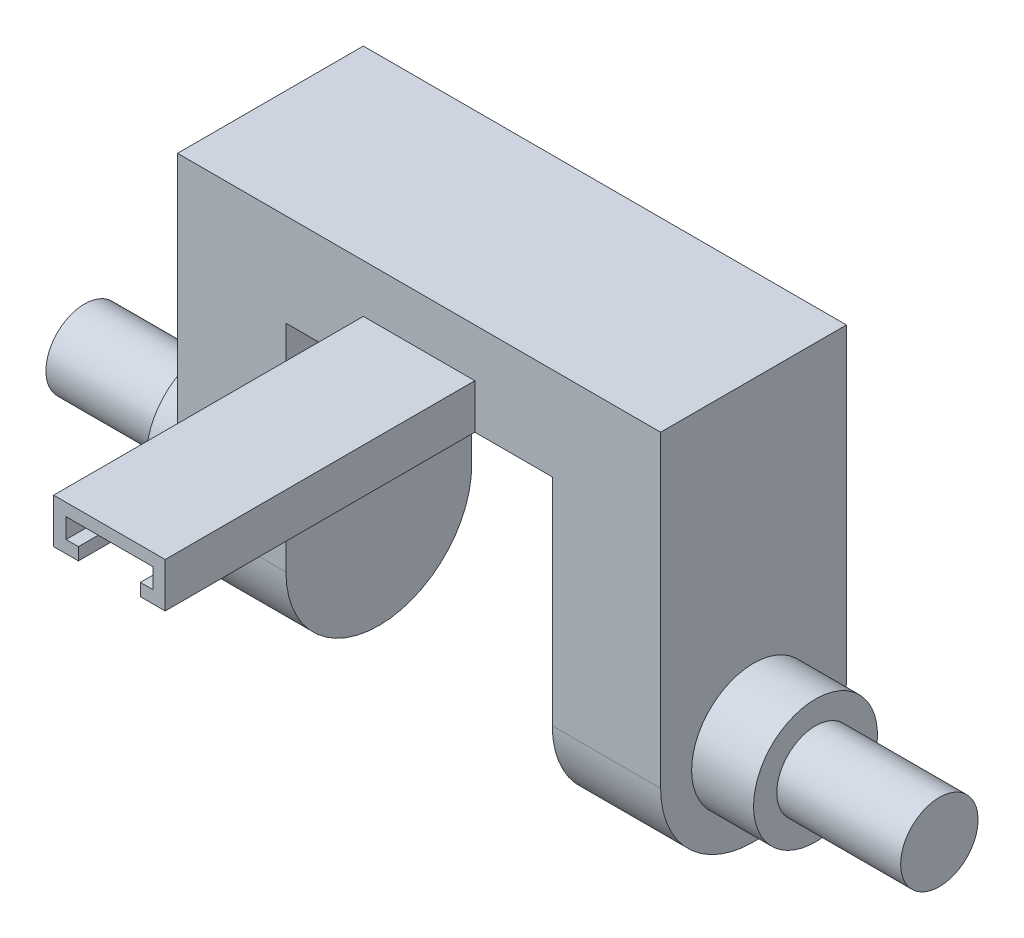
SolidWorks part; units mm, degrees
other "Markup1"
sketch "Sketch11" plane through (-87.63, 12.446, 0) normal (-0.7828, 0.0559, -0.6197) x (-0.6207, 0, 0.7841)
ref_plane "Front Plane" through (0, 0, 0) normal (0, 0, 1) x (1, 0, 0)
ref_plane "Top Plane" through (0, 0, 0) normal (0, 1, 0) x (1, 0, 0)
ref_plane "Right Plane" through (0, 0, 0) normal (1, 0, 0) x (0, 0, -1)
sketch "Sketch1" plane through (0, 0, 0) normal (0, 0, 1) x (1, 0, 0)
  line L0 (8.89, 0) -> (-8.89, 0)
  line L1 (-8.89, 0) -> (-8.89, -4.064)
  line L2 (-8.89, -4.064) -> (-6.35, -4.064)
  line L3 (-6.35, -4.064) -> (-6.35, -6.604)
  line L4 (-6.35, -6.604) -> (-11.43, -6.604)
  line L5 (-11.43, -6.604) -> (-11.43, 2.54)
  line L6 (-11.43, 2.54) -> (11.43, 2.54)
  line L7 (0, 2.54) -> (0, 0) construction
  line L8 (11.43, -6.604) -> (11.43, 2.54)
  line L9 (6.35, -6.604) -> (11.43, -6.604)
  line L10 (6.35, -4.064) -> (6.35, -6.604)
  line L11 (8.89, -4.064) -> (6.35, -4.064)
  line L12 (8.89, 0) -> (8.89, -4.064)
  dimension "D1" = 17.78
  dimension "D2" = 12.7
  dimension "D3" = 4.064
  dimension "D4" = 2.54
  dimension "D5" = 2.54
  dimension "D6" = 2.54
extrude "Rail Grip" add sketch "Sketch1" along normal blind 101.6
sketch "Sketch2" plane through (0, 0, 0) normal (0, -1, 0) x (1, 0, 0)
  line L1 (-3.175, 31.75) -> (3.175, 31.75)
  line L2 (-3.175, 31.75) -> (-3.175, 0)
  line L3 (-3.175, 0) -> (3.175, 0)
  line L4 (3.175, 31.75) -> (3.175, 0)
  line L5 (-3.175, 31.75) -> (3.175, 0) construction
  line L6 (-3.175, 0) -> (3.175, 31.75) construction
  point P0 (0, 15.875)
  dimension "D1" = 6.35
  dimension "D2" = 31.75
  dimension "D3" = 31.75
extrude "Rail Notch" add sketch "Sketch2" along normal blind 1.27
chamfer "Chamfer1" distance 0.254 angle 45 3 edges at (-3.175, -1.27, 15.875) (3.175, -1.27, 15.875) (0, -1.27, 31.75)
sketch "Sketch5" plane through (0, 0, 0) normal (0, 0, -1) x (-1, 0, 0)
  line L0 (8.89, -4.064) -> (8.89, -6.604)
  line L1 (11.43, -6.604) -> (6.35, -6.604) construction
  line L2 (8.89, -6.604) -> (6.35, -6.604)
  line L3 (6.35, -6.604) -> (6.35, -4.064)
  line L4 (6.35, -4.064) -> (8.89, -4.064)
  line L5 (-6.35, -4.064) -> (-8.89, -4.064)
  line L6 (-8.89, -4.064) -> (-8.89, -6.604)
  line L7 (-6.35, -6.604) -> (-11.43, -6.604) construction
  line L8 (-8.89, -6.604) -> (-6.35, -6.604)
  line L9 (-6.35, -6.604) -> (-6.35, -4.064)
extrude "Cut-Extrude1" cut sketch "Sketch5" against normal blind 53.975
sketch "Sketch4" plane through (0, 0, 0) normal (1, 0, 0) x (0, 0, -1)
  line L0 (0, 2.54) -> (0, 21.59)
  line L2 (-101.6, 2.54) -> (0, 2.54) construction
  line L3 (-65.0408, 2.54) -> (0, 2.54)
  line L4 (-32.5204, 35.0604) -> (-65.0408, 2.54)
  line L5 (0, -6.604) -> (0, 2.54) construction
  circle A1 centre (-19.05, 21.59) radius 7.9375
  arc A2 (0, 21.59) -> (-32.5204, 35.0604) centre (-19.05, 21.59) ccw
  dimension "D2" = 19.05
  dimension "D3" = 15.875
  dimension "D1" = 45
  dimension "D4" = 19.05
  dimension "D5" = 19.05
extrude "Boss-Extrude3" [suppressed] add sketch "Sketch4" along normal mid plane 22.86
sketch "Sketch6" plane through (0, 0, 0) normal (0, 0, -1) x (-1, 0, 0)
  line L0 (11.43, -6.604) -> (27.305, -6.604)
  line L1 (27.305, -6.604) -> (27.305, -70.104)
  line L2 (27.305, -70.104) -> (49.53, -70.104)
  line L3 (49.53, -70.104) -> (49.53, 12.446)
  line L5 (11.43, 2.54) -> (11.43, -6.604)
  line L6 (0, 0) -> (0, -1.27) construction
  line L7 (2.921, -1.27) -> (-2.921, -1.27) construction
  line L8 (11.43, 2.54) -> (-11.43, 2.54)
  line L11 (-49.53, 12.446) -> (49.53, 12.446)
  line L12 (-27.305, -70.104) -> (-49.53, -70.104)
  line L13 (-27.305, -6.604) -> (-27.305, -70.104)
  line L14 (-11.43, -6.604) -> (-27.305, -6.604)
  line L15 (-11.43, 2.54) -> (-11.43, -6.604)
  line L16 (-49.53, -70.104) -> (-49.53, 12.446)
  dimension "D1" = 15.875
  dimension "D2" = 63.5
  dimension "D3" = 38.1
  dimension "D4" = 19.05
extrude "Boss-Extrude4" add sketch "Sketch6" against normal blind 38.1
sketch "Sketch7" plane through (-49.53, 0, 0) normal (-1, 0, 0) x (0, 0, 1)
  line L15 (0, -70.104) -> (0, 12.446) construction
  circle A1 centre (19.05, -50.8) radius 7.9375
  dimension "D1" = 15.875
  dimension "D2" = 19.05
  dimension "D3" = 50.8
extrude "Boss-Extrude5" add sketch "Sketch7" along normal blind 38.1
sketch "Sketch9" plane through (-49.53, 0, 0) normal (-1, 0, 0) x (0, 0, 1)
  line L0 (0, -70.104) -> (0, 12.446) construction
  line L1 (38.1, -70.104) -> (38.1, 12.446) construction
  line L2 (38.1, -50.8) -> (38.1, -70.104)
  line L3 (38.1, -70.104) -> (0, -70.104)
  line L4 (0, -70.104) -> (0, -50.8)
  arc A0 (0, -50.8) -> (38.1, -50.8) centre (19.05, -50.8) ccw
extrude "Cut-Extrude2" cut sketch "Sketch9" against normal up to surface (99.06 mm away) up to face at (49.53, -28.829, 19.05)
sketch "Sketch10" plane through (-49.53, 0, 0) normal (-1, 0, 0) x (0, 0, 1)
  circle A0 centre (19.05, -50.8) radius 12.7
  dimension "D1" = 25.4
extrude "Boss-Extrude6" add sketch "Sketch10" along normal blind 12.7
mirror "Mirror1" about plane through (0, 0, 0) normal (1, 0, 0) of "Boss-Extrude6", "Boss-Extrude5"
